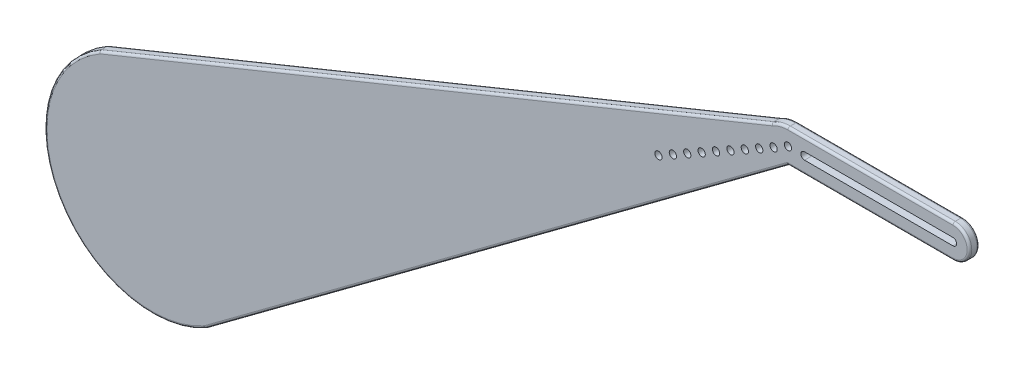
SolidWorks part; units mm, degrees
ref_plane "前视基准面" through (0, 0, 0) normal (0, 0, 1) x (1, 0, 0)
ref_plane "上视基准面" through (0, 0, 0) normal (0, 1, 0) x (1, 0, 0)
ref_plane "右视基准面" through (0, 0, 0) normal (1, 0, 0) x (0, 0, -1)
other "Configuration Table"
sketch "草图1" plane through (0, 0, 0) normal (0, 0, 1) x (1, 0, 0)
  line L0 (0, -55) -> (0, 55) construction
  line L1 (0, 5) -> (50, 5)
  line L3 (0, -5) -> (50, -5)
  line L5 (55, 0) -> (-55, 0) construction
  line L13 (0, -5) -> (-176.616, -136.1747)
  line L14 (-5, 3.6603) -> (-208.7523, -79.3156)
  arc A0 (50, -5) -> (50, 5) centre (50, 0) ccw
  arc A3 (0, 5) -> (-5, 3.6603) centre (0, -5) ccw
  arc A7 (-208.7523, -79.3156) -> (-176.616, -136.1747) centre (-192.6841, -107.7451) ccw
  dimension "D4" = 5
  dimension "D9" = 220
  dimension "D7" = 5
  dimension "D10" = 5
  dimension "D5" = 220
  dimension "D11" = 32.6562
  dimension "D1" = 50
  dimension "D2" = 10
  dimension "D3" = 5
  dimension "D6" = 202.158
  dimension "D8" = 143.398
extrude "凸台-拉伸1" add sketch "草图1" along normal blind 3
sketch "草图3" plane through (0, 0, 3) normal (0, 0, 1) x (1, 0, 0)
  line L1 (5, 1.1) -> (50, 1.1)
  line L3 (5, -1.1) -> (50, -1.1)
  line L5 (55, 0) -> (-55, 0) construction
  line L6 (0, -55) -> (0, 55) construction
  arc A0 (50, -1.1) -> (50, 1.1) centre (50, 0) ccw
  arc A1 (5, 1.1) -> (5, -1.1) centre (5, 0) ccw
  dimension "D5" = 45
  dimension "D1" = 1.1
  dimension "D4" = 1.1
  dimension "D2" = 2.2
  dimension "D3" = 1.1
  dimension "D6" = 5
  dimension "D7" = 5
extrude "切除-拉伸1" cut sketch "草图3" against normal blind 3
sketch "草图4" plane through (0, 0, 3) normal (0, 0, 1) x (1, 0, 0)
  line L0 (0, 0) -> (-221.1137, -123.8133)
  arc A1 (-208.7523, -79.3156) -> (-176.616, -136.1747) centre (-192.6841, -107.7451) ccw construction
ref_plane "基准面1" through (0, 0, 0) normal (-0.4886, 0.8725, 0) x (-0.8725, -0.4886, 0)
hole_wizard "Ø2.2 (2.2) 直径孔1" positions "草图7" profile "草图8" hole size "Ø2.2" standard "ANSI Metric" end condition up to next
sketch "草图7" plane through (0, 0, 3) normal (0, 0, 1) x (1, 0, 0)
  line L0 (0, 0) -> (-221.1137, -123.8133) construction
  line L1 (0, -1.65) -> (0, 1.65) construction
  point P1 (0, 0)
  dimension "D1" = 0
sketch "草图8" plane through (0, 0, 3) normal (1, 0, 0) x (0, -1, 0)
  line L0 (0, 0) -> (0, 3)
  line L1 (0, 3) -> (1.1, 3)
  line L2 (1.1, 3) -> (1.1, 0)
  line L5 (1.1, 0) -> (0, 0)
  line L11 (0, -6.35) -> (0, 107.95) construction
  dimension "通孔孔直径" = 2.2
  dimension "通孔孔深度" = 3
pattern_linear "阵列(线性)1" count 10 spacing 5 along (-0.8725, -0.4886, 0) of "Ø2.2 (2.2) 直径孔1"
fillet "圆角1" radius 0.7 14 edges at (55, 0, 0) (55, 0, 3) (25, 5, 3) (-2.5882, 4.6593, 3) (-2.5882, 4.6593, 0) (25, 5, 0) (25, -5, 0) (25, -5, 3) (-106.8762, -37.8277, 3) (-106.8762, -37.8277, 0) (-88.308, -70.5873, 0) (-88.308, -70.5873, 3) (-221.1137, -123.8133, 0) (-221.1137, -123.8133, 3)
